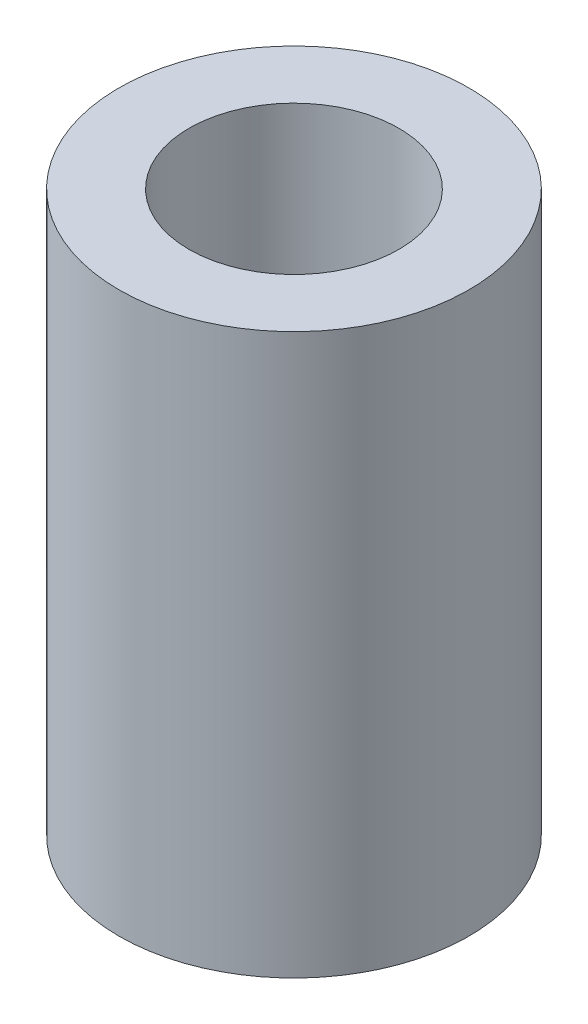
SolidWorks part; units mm, degrees
ref_plane "Front Plane" through (0, 0, 0) normal (0, 0, 1) x (1, 0, 0)
ref_plane "Top Plane" through (0, 0, 0) normal (0, 1, 0) x (1, 0, 0)
ref_plane "Right Plane" through (0, 0, 0) normal (1, 0, 0) x (0, 0, -1)
sketch "Sketch2" plane through (0, 0, 0) normal (0, 1, 0) x (1, 0, 0)
  circle A0 centre (0, 0) radius 2.5
  dimension "D1" = 5
extrude "Boss-Extrude1" add sketch "Sketch2" along normal blind 8
sketch "Sketch3" plane through (0, 8, 0) normal (0, 1, 0) x (1, 0, 0)
  circle A0 centre (0, 0) radius 1.5
  dimension "D1" = 3
extrude "Cut-Extrude1" cut sketch "Sketch3" against normal blind 6
